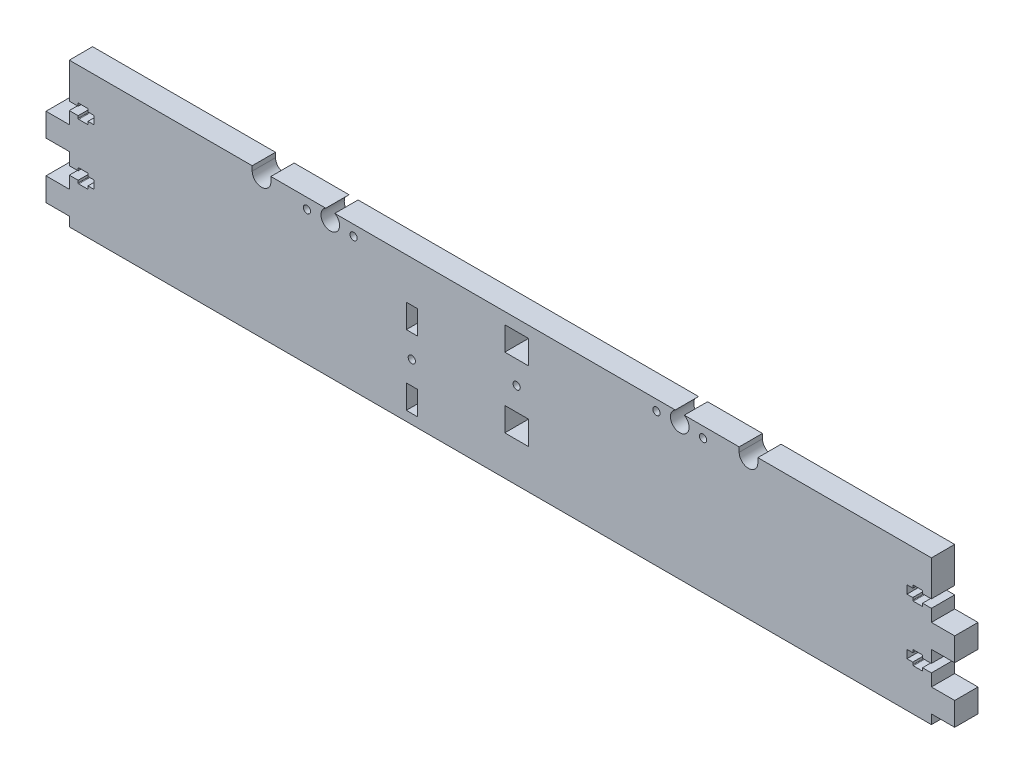
SolidWorks part; units mm, degrees
ref_plane "Front Plane" through (0, 0, 0) normal (0, 0, 1) x (1, 0, 0)
ref_plane "Top Plane" through (0, 0, 0) normal (0, 1, 0) x (1, 0, 0)
ref_plane "Right Plane" through (0, 0, 0) normal (1, 0, 0) x (0, 0, -1)
sketch "Sketch1" plane through (0, 0, 0) normal (0, 0, 1) x (1, 0, 0)
  line L0 (0, 0) -> (-185, 0)
  line L1 (-185, 0) -> (-185, -62) construction
  line L2 (0, -62) -> (-185, -62)
  line L3 (-185, -62) -> (-185, -58)
  line L4 (-185, -58) -> (-195, -58)
  line L5 (-195, -58) -> (-195, -48)
  line L6 (-195, -48) -> (-185, -48)
  line L7 (-185, -48) -> (-185, -34)
  line L8 (-185, -34) -> (-195, -34)
  line L9 (-195, -34) -> (-195, -24)
  line L10 (-195, -24) -> (-185, -24)
  line L11 (0, -62) -> (0, 0)
  line L12 (-185, -24) -> (-185, 0)
  line L13 (-195, -58) -> (-195, -24) construction
  line L14 (-195, -29) -> (-185, -29) construction
  line L15 (-195, -53) -> (-185, -53) construction
  dimension "D1" = 185
  dimension "D2" = 10
  dimension "D3" = 10
  dimension "D4" = 10
  dimension "D5" = 24
  dimension "D6" = 29
  dimension "D7" = 62
extrude "MainBody" add sketch "Sketch1" along normal blind 10
sketch "Sketch3" plane through (0, 0, 10) normal (0, 0, 1) x (1, 0, 0)
  line L0 (-185, -17) -> (-174.5, -17) construction
  line L1 (-185, 0) -> (-185, -24) construction
  line L2 (-185, -18.75) -> (-181.2, -18.75)
  line L3 (-181.2, -18.75) -> (-181.2, -19.75)
  line L4 (-180.95, -20) -> (-177.25, -20)
  line L5 (-177, -19.75) -> (-177, -18.75)
  line L6 (-177, -18.75) -> (-174.5, -18.75)
  line L7 (-174.5, -18.75) -> (-174.5, -15.25)
  line L8 (-181.2, -18.75) -> (-177, -18.75) construction
  line L9 (-195, -24) -> (-195, -34) construction
  line L10 (-181.2, -15.25) -> (-177, -15.25) construction
  line L11 (-177, -15.25) -> (-174.5, -15.25)
  line L12 (-177, -14.25) -> (-177, -15.25)
  line L13 (-180.95, -14) -> (-177.25, -14)
  line L14 (-181.2, -15.25) -> (-181.2, -14.25)
  line L15 (-185, -15.25) -> (-181.2, -15.25)
  line L16 (-185, -18.75) -> (-185, -15.25)
  line L17 (-185, -24) -> (-185, -34) construction
  line L19 (-195, -24) -> (-195, -34) construction
  line L20 (-195, -29) -> (-185, -29) construction
  line L21 (-181.2, -42.75) -> (-177, -42.75) construction
  line L22 (-181.2, -39.25) -> (-177, -39.25) construction
  line L23 (-185, -41) -> (-174.5, -41) construction
  line L24 (-185, -39.25) -> (-185, -42.75)
  line L25 (-185, -42.75) -> (-181.2, -42.75)
  line L26 (-181.2, -42.75) -> (-181.2, -43.75)
  line L27 (-180.95, -44) -> (-177.25, -44)
  line L28 (-177, -43.75) -> (-177, -42.75)
  line L29 (-177, -42.75) -> (-174.5, -42.75)
  line L30 (-174.5, -39.25) -> (-174.5, -42.75)
  line L31 (-177, -39.25) -> (-174.5, -39.25)
  line L32 (-177, -38.25) -> (-177, -39.25)
  line L33 (-180.95, -38) -> (-177.25, -38)
  line L34 (-181.2, -39.25) -> (-181.2, -38.25)
  line L35 (-185, -39.25) -> (-181.2, -39.25)
  line L36 (-181.2, -15.25) -> (-177, -15.25) construction
  arc A0 (-177.25, -20) -> (-177, -19.75) centre (-177.25, -19.75) ccw
  arc A1 (-181.2, -19.75) -> (-180.95, -20) centre (-180.95, -19.75) ccw
  arc A2 (-181.2, -14.25) -> (-180.95, -14) centre (-180.95, -14.25) cw
  arc A3 (-177.25, -14) -> (-177, -14.25) centre (-177.25, -14.25) cw
  arc A4 (-177.25, -44) -> (-177, -43.75) centre (-177.25, -43.75) ccw
  arc A5 (-181.2, -43.75) -> (-180.95, -44) centre (-180.95, -43.75) ccw
  arc A6 (-181.2, -38.25) -> (-180.95, -38) centre (-180.95, -38.25) cw
  arc A7 (-177.25, -38) -> (-177, -38.25) centre (-177.25, -38.25) cw
  point P6 (-195, -29)
  point P15 (-177, -20)
  point P18 (-181.2, -20)
  point P29 (-181.2, -14)
  point P30 (-177, -14)
  point P62 (-177, -44)
  point P63 (-181.2, -44)
  point P64 (-181.2, -38)
  point P65 (-177, -38)
  dimension "D2" = 8
  dimension "D7" = 0.25
  dimension "D1" = 10.5
  dimension "D3" = 1.75
  dimension "D4" = 3
  dimension "D5" = 12
  dimension "D6" = 4.2
extrude "ScrewCutouts" cut sketch "Sketch3" against normal through all
mirror "Mirror1" about plane through (0, 0, 0) normal (1, 0, 0) of "ScrewCutouts", "MainBody"
sketch "Sketch2" plane through (0, 0, 10) normal (0, 0, 1) x (1, 0, 0)
  line L0 (0, 0) -> (0, -62) construction
  line L1 (-185, -62) -> (185, -62) construction
  line L2 (2, 0) -> (2, -62) construction
  line L3 (185, 0) -> (-185, 0) construction
  line L4 (-63, -4.5) -> (-83, -4.5) construction
  line L5 (-73, -7.5) -> (-73, 0.5) construction
  line L6 (77, -7.5) -> (77, 0.5) construction
  line L7 (67, -4.5) -> (87, -4.5) construction
  circle A0 centre (-73, -3.5) radius 4
  circle A1 centre (-83, -4.5) radius 1.55
  circle A2 centre (-63, -4.5) radius 1.55
  circle A3 centre (67, -4.5) radius 1.55
  circle A4 centre (87, -4.5) radius 1.55
  circle A5 centre (77, -3.5) radius 4
  dimension "D1" = 3.1
  dimension "D2" = 8
  dimension "D4" = 3.5
  dimension "D5" = 75
  dimension "D6" = 2
  dimension "D3" = 10
  dimension "D7" = 1
extrude "RodCutouts" cut sketch "Sketch2" against normal through all
sketch "Sketch4" plane through (0, 0, 10) normal (0, 0, 1) x (1, 0, 0)
  line L0 (77, -3.5) -> (-73, -3.5) construction
  line L1 (2, -3.5) -> (2, -62) construction
  line L2 (-185, -62) -> (185, -62) construction
  line L3 (7, -45.1) -> (7, -4.9) construction
  line L4 (75.0635, 0) -> (-71.0635, 0) construction
  line L5 (7, -10) -> (7, -40) construction
  line L6 (1.9, -4.9) -> (12.1, -4.9)
  line L7 (1.9, -4.9) -> (1.9, -15.1)
  line L8 (1.9, -15.1) -> (12.1, -15.1)
  line L9 (12.1, -4.9) -> (12.1, -15.1)
  line L10 (1.9, -4.9) -> (12.1, -15.1) construction
  line L11 (1.9, -15.1) -> (12.1, -4.9) construction
  line L12 (1.9, -34.9) -> (12.1, -34.9)
  line L13 (1.9, -34.9) -> (1.9, -45.1)
  line L14 (1.9, -45.1) -> (12.1, -45.1)
  line L15 (12.1, -34.9) -> (12.1, -45.1)
  line L16 (1.9, -34.9) -> (12.1, -45.1) construction
  line L17 (1.9, -45.1) -> (12.1, -34.9) construction
  circle A0 centre (7, -25) radius 1.55
  point P12 (7, -10)
  point P17 (7, -40)
  dimension "D8" = 3.1
  dimension "D1" = 10.2
  dimension "D2" = 10.2
  dimension "D3" = 10.2
  dimension "D4" = 10.2
  dimension "D5" = 30
  dimension "D6" = 10
  dimension "D7" = 5
extrude "Cut-Extrude3" cut sketch "Sketch4" against normal through all
sketch "Sketch5" plane through (0, 0, 10) normal (0, 0, 1) x (1, 0, 0)
  line L0 (-38, 0) -> (-38, -62) construction
  line L1 (-74.9365, 0) -> (-185, 0) construction
  line L2 (-185, -62) -> (185, -62) construction
  line L3 (-40.35, -27.85) -> (-40.35, -47.65) construction
  line L4 (-40.35, -17.65) -> (-35.65, -17.65)
  line L5 (-40.35, -17.65) -> (-40.35, -27.85)
  line L6 (-40.35, -27.85) -> (-35.65, -27.85)
  line L7 (-35.65, -17.65) -> (-35.65, -27.85)
  line L8 (-40.35, -17.65) -> (-35.65, -27.85) construction
  line L9 (-40.35, -27.85) -> (-35.65, -17.65) construction
  line L10 (-40.35, -47.65) -> (-35.65, -47.65)
  line L11 (-40.35, -47.65) -> (-40.35, -57.85)
  line L12 (-40.35, -57.85) -> (-35.65, -57.85)
  line L13 (-35.65, -47.65) -> (-35.65, -57.85)
  line L14 (-40.35, -47.65) -> (-35.65, -57.85) construction
  line L15 (-40.35, -57.85) -> (-35.65, -47.65) construction
  line L16 (-35.65, -47.65) -> (-35.65, -27.85) construction
  line L17 (-40.35, -37.75) -> (-35.65, -37.75) construction
  line L18 (-73, -3.5) -> (77, -3.5) construction
  line L19 (2, -3.5) -> (2, -62) construction
  line L20 (2, -32.75) -> (-195, -32.75) construction
  line L21 (-195, -24) -> (-195, -34) construction
  line L22 (-31.45, 8.9944) -> (-31.45, 5) construction
  line L23 (75.0635, 0) -> (-71.0635, 0) construction
  line L24 (-28.25, 8.9944) -> (-28.25, 5)
  line L25 (-34.65, 8.9944) -> (-34.65, 5)
  circle A0 centre (-38, -37.75) radius 1.55
  arc A1 (-28.25, 8.9944) -> (-34.65, 8.9944) centre (-31.45, 8.9944) ccw
  arc A2 (-34.65, 5) -> (-28.25, 5) centre (-31.45, 5) ccw
  point P6 (-38, -22.75)
  point P11 (-38, -52.75)
  point P34 (-31.45, 6.9972)
  dimension "D3" = 10.2
  dimension "D4" = 10.2
  dimension "D5" = 30
  dimension "D6" = 3.1
  dimension "D9" = 3.2
  dimension "D1" = 4.7
  dimension "D2" = 0
  dimension "D7" = 40
  dimension "D8" = 5
  dimension "D10" = 5
  dimension "D11" = 1
extrude "EndstopHolder" cut sketch "Sketch5" against normal through all
sketch "Sketch6" plane through (0, 0, 10) normal (0, 0, 1) x (1, 0, 0)
  line L0 (-40.35, -47.65) -> (-40.35, -27.85) construction
  line L1 (-42.35, -47.65) -> (-27.65, -47.65) construction
  line L3 (-27.65, -53.65) -> (-27.65, -41.65) construction
  line L4 (-29.65, -53.65) -> (-29.65, -41.65)
  line L5 (-25.65, -53.65) -> (-25.65, -41.65)
  line L6 (-35.65, -47.65) -> (-40.35, -47.65) construction
  line L7 (-35.65, -57.85) -> (-35.65, -47.65) construction
  arc A0 (-29.65, -53.65) -> (-25.65, -53.65) centre (-27.65, -53.65) ccw
  arc A1 (-25.65, -41.65) -> (-29.65, -41.65) centre (-27.65, -41.65) ccw
  point P10 (-27.65, -47.65)
  dimension "D1" = 2
  dimension "D2" = 12
  dimension "D3" = 8
  dimension "D4" = 0
extrude "EndstopWires" [suppressed] cut sketch "Sketch6" against normal through all
sketch "Sketch7" plane through (0, 0, 10) normal (0, 0, 1) x (1, 0, 0)
  line L0 (-73, -3.5) -> (77, -3.5) construction
  line L1 (2, -3.5) -> (2, -62) construction
  line L3 (-102.5, 0) -> (-102.5, -2) construction
  line L4 (-74.9365, 0) -> (-185, 0) construction
  line L5 (-98.5, 0) -> (-98.5, -2)
  line L6 (-106.5, 0) -> (-106.5, -2)
  line L7 (106.5, 0) -> (106.5, -2) construction
  line L8 (102.5, 0) -> (102.5, -2)
  line L9 (110.5, 0) -> (110.5, -2)
  line L10 (-185, -62) -> (185, -62) construction
  arc A0 (-98.5, 0) -> (-106.5, 0) centre (-102.5, 0) ccw
  arc A1 (-106.5, -2) -> (-98.5, -2) centre (-102.5, -2) ccw
  arc A2 (102.5, 0) -> (110.5, 0) centre (106.5, 0) cw
  arc A3 (110.5, -2) -> (102.5, -2) centre (106.5, -2) cw
  point P12 (-102.5, -1)
  point P19 (106.5, -1)
  dimension "D3" = 4
  dimension "D1" = 2
  dimension "D2" = 104.5
extrude "Cut-Extrude4" cut sketch "Sketch7" against normal through all
equation "\"Y-ROD-SPACING\"=75"
equation "\"D5@Sketch2\"=\"Y-ROD-SPACING\""
equation "\"Y-BED-OFFSET\"=2"
equation "\"D6@Sketch2\"=\"Y-BED-OFFSET\""
equation "\"T-SLOT-NUT-FILLET-RADIUS\"=0.25"
equation "\"D7@Sketch3\"=\"T-SLOT-NUT-FILLET-RADIUS\""
equation "\"T-SLOT-SCREW-SHAFT-RADIUS\"=1.75"
equation "\"D3@Sketch3\"=\"T-SLOT-SCREW-SHAFT-RADIUS\""
equation "\"T-SLOT-SCREW-SHAFT-CUTOUT-LENGTH\"=10.5"
equation "\"D1@Sketch3\"=\"T-SLOT-SCREW-SHAFT-CUTOUT-LENGTH\""
equation "\"T-SLOT-NUT-DEPTH\"=4.2"
equation "\"D6@Sketch3\"=\"T-SLOT-NUT-DEPTH\""
equation "\"T-SLOT-NUT-WIDTH\"=3"
equation "\"D4@Sketch3\"=\"T-SLOT-NUT-WIDTH\""
equation "\"T-SLOT-NUT-END-DISTANCE\"=8"
equation "\"D2@Sketch3\"=\"T-SLOT-NUT-END-DISTANCE\""
equation "\"ACRYLIC-TAB-CUTOUT-SIZE\"=\"ACRYLIC-THICKNESS\"+\"ACRYLIC-TAB-TOLERANCE\"*2"
equation "\"D1@Sketch4\"=\"ACRYLIC-TAB-CUTOUT-SIZE\""
equation "\"D2@Sketch4\"=\"ACRYLIC-TAB-CUTOUT-SIZE\""
equation "\"D3@Sketch4\"=\"ACRYLIC-TAB-CUTOUT-SIZE\""
equation "\"D4@Sketch4\"=\"ACRYLIC-TAB-CUTOUT-SIZE\""
equation "\"ACRYLIC-M3-HOLE\"=3.1"
equation "\"D8@Sketch4\"=\"ACRYLIC-M3-HOLE\""
equation "\"Y-BED-ROD-INSET\"=3.5"
equation "\"D1@Sketch2\"=\"ACRYLIC-M3-HOLE\""
equation "\"D4@Sketch2\"=\"Y-BED-ROD-INSET\""
equation "\"SMOOTHROD-CAP-SCREW-DISTANCE\"=20"
equation "\"D3@Sketch2\"=\"SMOOTHROD-CAP-SCREW-DISTANCE\"/2"
equation "\"ACRYLIC-TAB-WIDTH\"=\"ACRYLIC-THICKNESS\""
equation "\"FRAME-WIDTH-INNER\"=370"
equation "\"D2@Sketch1\"=\"ACRYLIC-TAB-WIDTH\""
equation "\"D3@Sketch1\"=\"ACRYLIC-TAB-WIDTH\""
equation "\"D4@Sketch1\"=\"ACRYLIC-TAB-WIDTH\""
equation "\"D1@Sketch1\"=\"FRAME-WIDTH-INNER\"/2"
equation "\"X-ROD-SPACING\"=45"
equation "\"Z-ROD-SPACING\"=17.5"
equation "\"ACRYLIC-THICKNESS\"=10"
equation "\"ACRYLIC-THICKNESS2\"=4.5"
equation "\"NEMA17-HOLE-SPACING\"=31"
equation "\"NEMA17-CENTRAL-CUTOUT\"=22.5"
equation "\"Z-BRACKET-REACH\"=55"
equation "\"TOP-BRACKET-SPACING\"=40"
equation "\"SMOOTHROD-X-LENGTH\"=350"
equation "\"SMOOTHROD-Y-LENGTH\"=350"
equation "\"SMOOTHROD-Z-LENGTH\"=350"
equation "\"SMOOTHROD-TIGHTENING-HEADROOM\"=.25"
equation "\"LEADSCREW-Z-LENGTH\"=300"
equation "\"SCREW-LENGTH-FRAME\"=\"ACRYLIC-THICKNESS\" + 10"
equation "\"SCREW-HEAD-RADIUS\"=6"
equation "\"PRINTED-X-SMOOTHROD-DIAMETER\"=8.2"
equation "\"PRINTED-X-SMOOTHROD-CUTOUT\"=10"
equation "\"PRINTED-X-BASE-HEIGHT\"=10"
equation "\"PRINTED-LM8UU-CUTOUT-SIZE\"=15.25"
equation "\"PRINTED-LM8UU-CUTOUT-LENGTH\"=24.5"
equation "\"PRINTED-X-IDLER-HEIGHT\"=16"
equation "\"PSU-MOUNTING-WIDTH\"=95"
equation "\"PSU-MOUNTING-HEIGHT\"=177"
equation "\"D1@MainBody\"=\"ACRYLIC-THICKNESS\""
equation "\"D1@Sketch5\"=\"ACRYLIC-THICKNESS2\"+\"ACRYLIC-TAB-TOLERANCE\"*2"
equation "\"D3@Sketch5\"=\"ACRYLIC-TAB-CUTOUT-SIZE\""
equation "\"D4@Sketch5\"=\"ACRYLIC-TAB-CUTOUT-SIZE\""
equation "\"D6@Sketch5\"=\"ACRYLIC-M3-HOLE\""
equation "\"Y-BED-SCREW-SPACING\"=209"
equation "\"Y-BED-SCREW-CUTOUT-SLOT-HEIGHT\"=2"
equation "\"Z-ROD-INSET\"=16"
equation "\"Y-BELT-TO-ROD-DISTANCE\"=20"
equation "\"SPOOL-HOLDER-ROD-SPACING\"=150"
equation "\"D1@Sketch7\"=\"Y-BED-SCREW-CUTOUT-SLOT-HEIGHT\""
equation "\"D2@Sketch7\"=\"Y-BED-SCREW-SPACING\"/2"
equation "\"ACRYLIC-TAB-TOLERANCE\"=.1"
equation "\"SCREW-LENGTH-MOTOR\"=\"ACRYLIC-THICKNESS\" + 5"
equation "\"SCREW-LENGTH-EXTRUDER\"=28"
equation "\"ACRYLIC-X-CARRIAGE-WIDTH\"=55"
equation "\"ACRYLIC-X-CARRIAGE-HEIGHT\"=75"
equation "\"ACRYLIC-X-CARRIAGE-LM8UU-CUTOUT-WIDTH\"=24.25"
equation "\"ACRYLIC-X-CARRIAGE-SCREW-SPACING-X\"=15"
equation "\"ACRYLIC-X-CARRIAGE-SCREW-SPACING-Y\"=33"
equation "\"ACRYLIC-X-CARRIAGE-CENTER-TAB-SPACING\"=14"
equation "\"ACRYLIC-X-CARRIAGE-EXTRUDER-OFFSET\"=26"
equation "\"ACRYLIC-X-CARRIAGE-EXTRUDER-ANGLE\"=90"
equation "\"ACRYLIC-X-CARRIAGE-EXTRUDER-SHELF-DEPTH\"=\"ACRYLIC-X-CARRIAGE-EXTRUDER-OFFSET\" + 28"
equation "\"ACRYLIC-X-CARRIAGE-EXTRUDER-BRACE-SPACING\"=23"
equation "\"ACRYLIC-X-CARRIAGE-EXTRUDER-BRACE-TAB-OFFSET\"=20"
equation "\"ACRYLIC-X-CARRIAGE-EXTRUDER-BRACE-HEIGHT\"=35"
equation "\"ACRYLIC-X-CARRIAGE-EXTRUDER-BRACE-SCREW-SPACING\"=22"
equation "\"PRINTED-M3-HOLE\"=3.5"
equation "\"ACRYLIC-X-CARRIAGE-LM8UU-CUTOUT-HEIGHT\"=11.5"
equation "\"ACRYLIC-X-CARRIAGE-DUAL-WIDTH-MULTIPLIER\"=1.65"
equation "\"ACRYLIC-X-CARRIAGE-DUAL-HOTEND-SPACING\"=42"
equation "\"ACRYLIC-X-CARRIAGE-DUAL-WIDTH\"=95"
equation "\"ACRYLIC-X-CARRIAGE-DUAL-HOTEND-SEPARATION\"=35"
equation "\"ACRYLIC-X-CARRIAGE-DUAL-MOUNT-PLATE-DEPTH\"=75"
equation "\"ACRYLIC-X-CARRIAGE-DUAL-MOUNT-BRACE-WIDTH\"=33"
equation "\"ACRYLIC-X-CARRIAGE-DUAL-MOUNT-SCREW-WIDTH\"=40"
equation "\"BLOWER-FAN-WIDTH\"=15"
